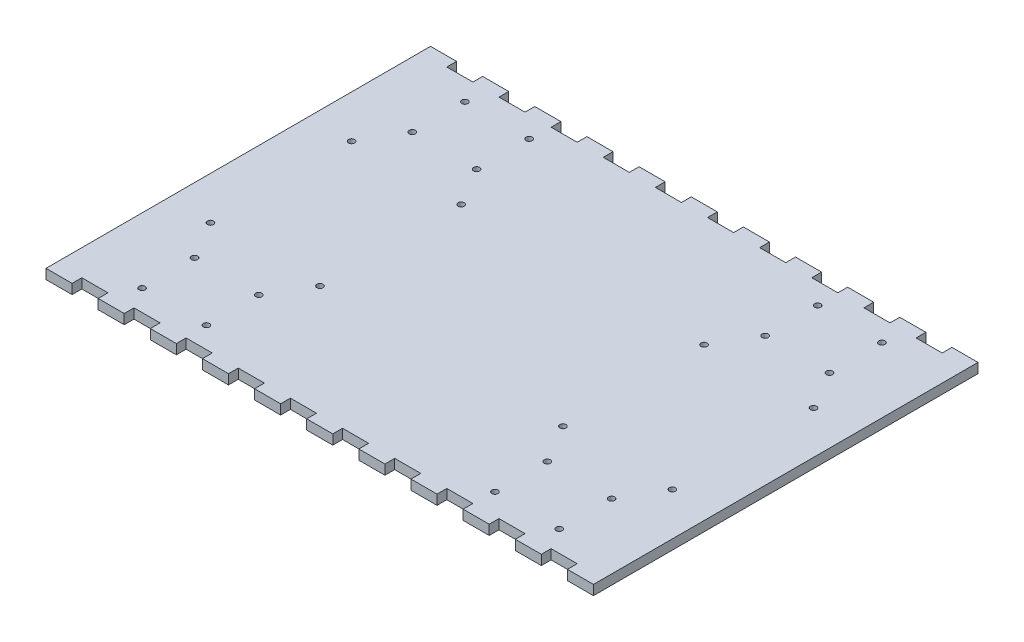
SolidWorks part; units mm, degrees
ref_plane "Front Plane" through (0, 0, 0) normal (0, 0, 1) x (1, 0, 0)
ref_plane "Top Plane" through (0, 0, 0) normal (0, 1, 0) x (1, 0, 0)
ref_plane "Right Plane" through (0, 0, 0) normal (1, 0, 0) x (0, 0, -1)
sketch "Sketch2" plane through (0, 0, 0) normal (0, 1, 0) x (1, 0, 0)
  line L11 (25.4, 88.9) -> (25.4, 93.6625)
  line L12 (12.7, -88.9) -> (25.4, -88.9)
  line L23 (0, -88.9) -> (0, 88.9)
  line L24 (12.7, 88.9) -> (25.4, 88.9)
  line L29 (266.7, -88.9) -> (266.7, 88.9)
  line L30 (25.4, 93.6625) -> (38.1, 93.6625)
  line L35 (38.1, 88.9) -> (38.1, 93.6625)
  line L41 (0, 88.9) -> (0, 93.6625)
  line L42 (0, 93.6625) -> (12.7, 93.6625)
  line L47 (12.7, 88.9) -> (12.7, 93.6625)
  line L48 (50.8, 88.9) -> (50.8, 93.6625)
  line L53 (50.8, 93.6625) -> (63.5, 93.6625)
  line L54 (63.5, 88.9) -> (63.5, 93.6625)
  line L59 (76.2, 88.9) -> (76.2, 93.6625)
  line L60 (76.2, 93.6625) -> (88.9, 93.6625)
  line L65 (88.9, 88.9) -> (88.9, 93.6625)
  line L66 (101.6, 88.9) -> (101.6, 93.6625)
  line L71 (101.6, 93.6625) -> (114.3, 93.6625)
  line L72 (114.3, 88.9) -> (114.3, 93.6625)
  line L77 (127, 88.9) -> (127, 93.6625)
  line L78 (127, 93.6625) -> (139.7, 93.6625)
  line L79 (139.7, 88.9) -> (139.7, 93.6625)
  line L80 (152.4, 88.9) -> (152.4, 93.6625)
  line L81 (152.4, 93.6625) -> (165.1, 93.6625)
  line L82 (165.1, 88.9) -> (165.1, 93.6625)
  line L83 (177.8, 88.9) -> (177.8, 93.6625)
  line L84 (177.8, 93.6625) -> (190.5, 93.6625)
  line L85 (190.5, 88.9) -> (190.5, 93.6625)
  line L86 (203.2, 88.9) -> (203.2, 93.6625)
  line L87 (203.2, 93.6625) -> (215.9, 93.6625)
  line L88 (215.9, 88.9) -> (215.9, 93.6625)
  line L89 (228.6, 88.9) -> (228.6, 93.6625)
  line L90 (228.6, 93.6625) -> (241.3, 93.6625)
  line L91 (241.3, 88.9) -> (241.3, 93.6625)
  line L92 (254, 88.9) -> (254, 93.6625)
  line L93 (254, 93.6625) -> (266.7, 93.6625)
  line L94 (266.7, 88.9) -> (266.7, 93.6625)
  line L95 (38.1, 88.9) -> (50.8, 88.9)
  line L96 (63.5, 88.9) -> (76.2, 88.9)
  line L97 (88.9, 88.9) -> (101.6, 88.9)
  line L98 (114.3, 88.9) -> (127, 88.9)
  line L99 (139.7, 88.9) -> (152.4, 88.9)
  line L100 (165.1, 88.9) -> (177.8, 88.9)
  line L101 (190.5, 88.9) -> (203.2, 88.9)
  line L102 (215.9, 88.9) -> (228.6, 88.9)
  line L103 (241.3, 88.9) -> (254, 88.9)
  line L104 (0, 0) -> (266.7, 0) construction
  line L105 (241.3, -88.9) -> (254, -88.9)
  line L106 (215.9, -88.9) -> (228.6, -88.9)
  line L107 (190.5, -88.9) -> (203.2, -88.9)
  line L108 (165.1, -88.9) -> (177.8, -88.9)
  line L109 (139.7, -88.9) -> (152.4, -88.9)
  line L110 (114.3, -88.9) -> (127, -88.9)
  line L111 (88.9, -88.9) -> (101.6, -88.9)
  line L112 (63.5, -88.9) -> (76.2, -88.9)
  line L113 (38.1, -88.9) -> (50.8, -88.9)
  line L114 (266.7, -88.9) -> (266.7, -93.6625)
  line L115 (254, -93.6625) -> (266.7, -93.6625)
  line L116 (254, -88.9) -> (254, -93.6625)
  line L117 (241.3, -88.9) -> (241.3, -93.6625)
  line L118 (228.6, -93.6625) -> (241.3, -93.6625)
  line L119 (228.6, -88.9) -> (228.6, -93.6625)
  line L120 (215.9, -88.9) -> (215.9, -93.6625)
  line L121 (203.2, -93.6625) -> (215.9, -93.6625)
  line L122 (203.2, -88.9) -> (203.2, -93.6625)
  line L123 (190.5, -88.9) -> (190.5, -93.6625)
  line L124 (177.8, -93.6625) -> (190.5, -93.6625)
  line L125 (177.8, -88.9) -> (177.8, -93.6625)
  line L126 (165.1, -88.9) -> (165.1, -93.6625)
  line L127 (152.4, -93.6625) -> (165.1, -93.6625)
  line L128 (152.4, -88.9) -> (152.4, -93.6625)
  line L129 (139.7, -88.9) -> (139.7, -93.6625)
  line L130 (127, -93.6625) -> (139.7, -93.6625)
  line L131 (127, -88.9) -> (127, -93.6625)
  line L132 (114.3, -88.9) -> (114.3, -93.6625)
  line L133 (101.6, -93.6625) -> (114.3, -93.6625)
  line L134 (101.6, -88.9) -> (101.6, -93.6625)
  line L135 (88.9, -88.9) -> (88.9, -93.6625)
  line L136 (76.2, -93.6625) -> (88.9, -93.6625)
  line L137 (76.2, -88.9) -> (76.2, -93.6625)
  line L138 (63.5, -88.9) -> (63.5, -93.6625)
  line L139 (50.8, -93.6625) -> (63.5, -93.6625)
  line L140 (50.8, -88.9) -> (50.8, -93.6625)
  line L141 (12.7, -88.9) -> (12.7, -93.6625)
  line L142 (0, -93.6625) -> (12.7, -93.6625)
  line L143 (0, -88.9) -> (0, -93.6625)
  line L144 (38.1, -88.9) -> (38.1, -93.6625)
  line L145 (25.4, -93.6625) -> (38.1, -93.6625)
  line L146 (12.7, -88.9) -> (25.4, -88.9)
  line L147 (25.4, -88.9) -> (25.4, -93.6625)
  line L148 (38.1, -88.9) -> (50.8, -88.9)
  line L149 (63.5, -88.9) -> (76.2, -88.9)
  line L150 (88.9, -88.9) -> (101.6, -88.9)
  line L151 (114.3, -88.9) -> (127, -88.9)
  line L152 (139.7, -88.9) -> (152.4, -88.9)
  line L153 (165.1, -88.9) -> (177.8, -88.9)
  line L154 (190.5, -88.9) -> (203.2, -88.9)
  line L155 (215.9, -88.9) -> (228.6, -88.9)
  line L156 (241.3, -88.9) -> (254, -88.9)
  dimension "D1" = 177.8
  dimension "D2" = 266.7
  dimension "D3" = 12.7
  dimension "D4" = 4.7625
extrude "Boss-Extrude1" add sketch "Sketch2" along normal blind 4.7625 contours L12 L147 L145 L144 L113 L140 L139 L138 L112 L137 L136 L135 L111 L134 L133 L132 L110 L131 L130 L129 L109 L128 L127 L126 L108 L125 L124 L123 L107 L122 L121 L120 L106 L119 L118 L117 L105 L116 L115 L114 L29 L94 L93 L92 L103 L91 L90 L89 L102 L88 L87 | L23 L104 L29 L94 L93 L92 L103 L91 L90 L89 L102 L88 L87 L86 L101 L85 L84 L83 L100 L82 L81 L80 L99 L79 L78 L77 L98 L72 L71 L66 L97 L65 L60 L59 L96 L54 L53 L48 L95 L35 L30 L11 L24 L47 L42 L41 region at (133.35, 0, -45.7283) region at (133.35, 0, 45.7283)
sketch "Sketch5" plane through (0, 4.7625, 0) normal (0, 1, 0) x (1, 0, 0)
  line L1 (25.4, 93.6625) -> (38.1, 93.6625) construction
  line L3 (0, 93.6625) -> (12.7, 93.6625) construction
  line L5 (0, 0) -> (266.7, 0) construction
  line L6 (0, -93.6625) -> (0, 93.6625) construction
  line L7 (266.7, 93.6625) -> (266.7, -93.6625) construction
  circle A0 centre (31.75, 78.6125) radius 1.5
  circle A1 centre (63.07, 78.6125) radius 1.5
  circle A2 centre (63.07, 53.0625) radius 1.5
  circle A3 centre (31.75, 53.0625) radius 1.5
  circle A20 centre (203.63, 78.6125) radius 1.5
  circle A21 centre (203.63, 53.0625) radius 1.5
  circle A22 centre (234.95, 53.0625) radius 1.5
  circle A23 centre (234.95, 78.6125) radius 1.5
  circle A24 centre (234.95, -78.6125) radius 1.5
  circle A25 centre (234.95, -53.0625) radius 1.5
  circle A26 centre (203.63, -53.0625) radius 1.5
  circle A27 centre (203.63, -78.6125) radius 1.5
  circle A28 centre (31.75, -53.0625) radius 1.5
  circle A29 centre (63.07, -53.0625) radius 1.5
  circle A30 centre (63.07, -78.6125) radius 1.5
  circle A31 centre (31.75, -78.6125) radius 1.5
  circle A32 centre (20.83, 34.385) radius 1.5
  circle A33 centre (74.17, 34.385) radius 1.5
  circle A34 centre (192.53, 34.385) radius 1.5
  circle A35 centre (245.87, 34.385) radius 1.5
  circle A36 centre (245.87, -34.385) radius 1.5
  circle A37 centre (192.53, -34.385) radius 1.5
  circle A38 centre (74.17, -34.385) radius 1.5
  circle A39 centre (20.83, -34.385) radius 1.5
  point P3 (64.57, 78.6125)
  point P7 (30.25, 78.6125)
  point P23 (31.75, 93.6625)
  point P50 (31.75, 80.1125)
  point P51 (31.75, 51.5625)
  dimension "D1" = 28.55
  dimension "D3" = 3
  dimension "D4" = 2
  dimension "D2" = 13.55
  dimension "D5" = 34.32
  dimension "D6" = 31.75
  dimension "D7" = 20.83
  dimension "D8" = 53.34
  dimension "D9" = 59.2775
  dimension "D11" = 20.83
  dimension "D10" = 2
extrude "Cut-Extrude1" cut sketch "Sketch5" against normal through all
sketch "Sketch6" plane through (0, 4.7625, 0) normal (0, 1, 0) x (1, 0, 0)
  line L0 (0, -93.6625) -> (0, 93.6625) construction
  line L1 (0, 93.6625) -> (12.7, 93.6625) construction
  text T0 "TREY MADE THIS CHASSIS\r\n the robot will be on this\r\n<i>      -\"Danny Devito\"</i>"
  dimension "D1" = 101.6
  dimension "D2" = 82.677
